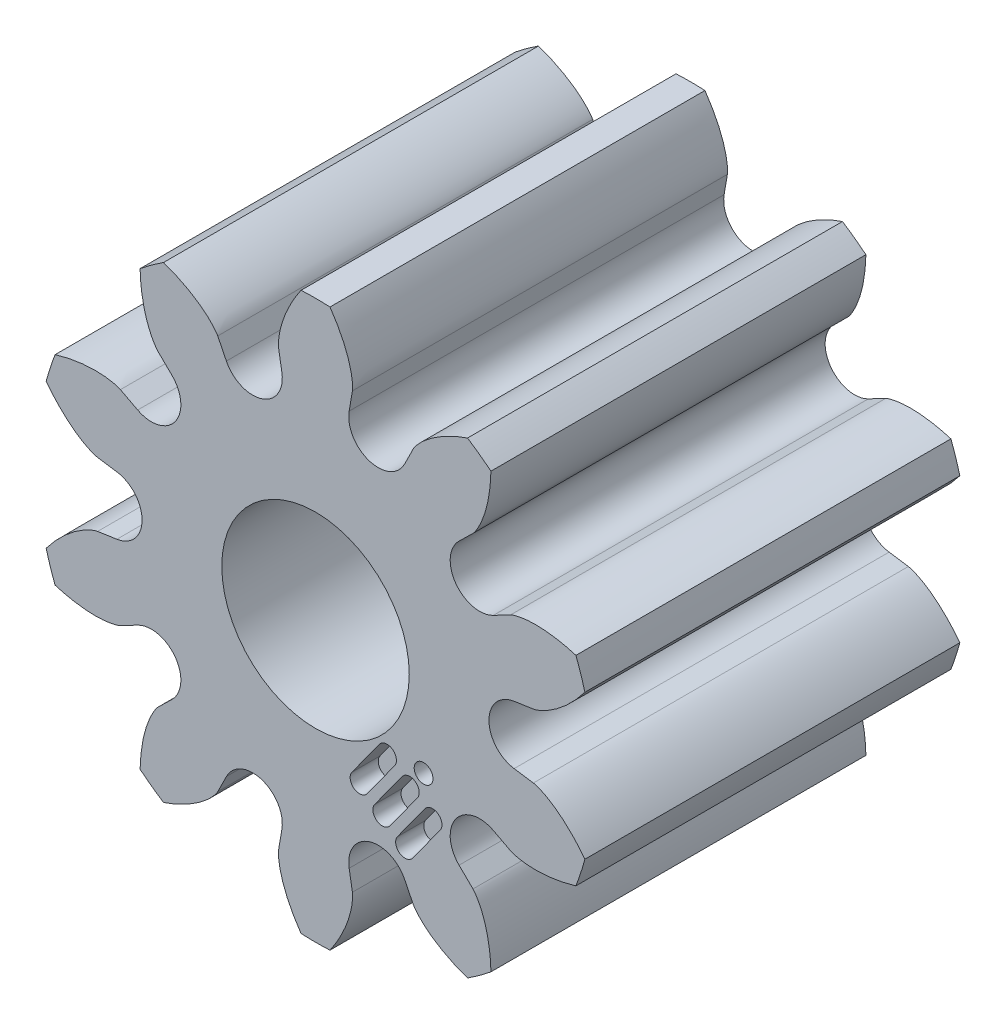
SolidWorks part; units mm, degrees
ref_plane "Front Plane" through (0, 0, 0) normal (0, 0, 1) x (1, 0, 0)
ref_plane "Top Plane" through (0, 0, 0) normal (0, 1, 0) x (1, 0, 0)
ref_plane "Right Plane" through (0, 0, 0) normal (1, 0, 0) x (0, 0, -1)
ref_axis "Axis1" through (0, 0, 4.2) along (0, 0, -1)
sketch "Sketch2" plane through (0, 0, 0) normal (0, 0, 1) x (1, 0, 0)
  circle A0 centre (0, 0) radius 2.975
  dimension "D1" = 5.95
extrude "Boss-Extrude1" add sketch "Sketch2" along normal blind 4
sketch "Sketch1" plane through (0, 0, 0) normal (0, 0, 1) x (1, 0, 0)
  line L1 (2.3243, 0.3413) -> (1.8304, 0.2688) construction
  line L3 (1.8304, -0.2688) -> (2.3243, -0.3413) construction
  line L4 (3.8854, 0) -> (4.3327, 0) construction
  line L6 (2.1188, 0.3112) -> (2.3243, 0.3413)
  line L7 (2.1188, -0.3112) -> (2.3243, -0.3413)
  circle A0 centre (0, 0) radius 1.85 construction
  circle A1 centre (0, 0) radius 2.3492 construction
  circle A6 centre (0, 0) radius 2.975 construction
  arc A7 (2.9584, 0.8934) -> (2.9584, -0.8934) centre (0, 0) cw
  arc A8 (1.8304, 0.2688) -> (1.8304, -0.2688) centre (0, 0) cw construction
  arc A9 (1.85, 0) -> (2.1188, 0.3112) centre (2.1645, 0) cw
  circle A11 centre (0, 0) radius 2.975 construction
  arc A12 (2.3243, 0.3413) -> (2.3243, -0.3413) centre (0, 0) cw construction
  arc A13 (1.85, 0) -> (2.1188, -0.3112) centre (2.1645, 0) ccw
  spline S0 degree 4 poles (2.3243, 0.3413) (2.3278, 0.3419) (2.3344, 0.3434) (2.345, 0.3462) (2.3658, 0.3527) (2.3888, 0.3614) (2.4144, 0.3725) (2.4415, 0.3858) (2.4643, 0.3979) (2.4867, 0.4108) (2.5087, 0.4242) (2.535, 0.4413) (2.5661, 0.4628) (2.6015, 0.4895) (2.6407, 0.5215) (2.6795, 0.5559) (2.7167, 0.5913) (2.7532, 0.6287) (2.7876, 0.666) (2.8221, 0.7064) (2.8532, 0.7446) (2.8867, 0.789) (2.9133, 0.8254) (2.9467, 0.8752) (2.966, 0.9051) (2.988, 0.9407) (2.9974, 0.9568) (3.0033, 0.9667) knots 0 0 0 0 0 0.015084 0.028532 0.04661 0.092111 0.119476 0.146842 0.174209 0.201575 0.228941 0.256307 0.307035 0.361767 0.4165 0.471232 0.525964 0.580697 0.635429 0.690161 0.744894 0.799626 0.854358 0.909091 0.954545 1 1 1 1 1 construction
  spline S1 degree 4 poles (2.3243, 0.3413) (2.3278, 0.3419) (2.3344, 0.3434) (2.345, 0.3462) (2.3658, 0.3527) (2.3888, 0.3614) (2.4144, 0.3725) (2.4415, 0.3858) (2.4643, 0.3979) (2.4867, 0.4108) (2.5087, 0.4242) (2.535, 0.4413) (2.5661, 0.4628) (2.6015, 0.4895) (2.6407, 0.5215) (2.6795, 0.5559) (2.7167, 0.5913) (2.7532, 0.6287) (2.7876, 0.666) (2.8221, 0.7064) (2.8532, 0.7446) (2.8867, 0.789) (2.9133, 0.8254) (2.9395, 0.8644) (2.9521, 0.8835) (2.9584, 0.8934) knots 0 0 0 0 0 0.015084 0.028532 0.04661 0.092111 0.119476 0.146842 0.174209 0.201575 0.228941 0.256307 0.307035 0.361767 0.4165 0.471232 0.525964 0.580697 0.635429 0.690161 0.744894 0.799626 0.854358 0.909091 0.909091 0.909091 0.909091 0.909091
  spline S2 degree 4 poles (2.3243, -0.3413) (2.3278, -0.3419) (2.3344, -0.3434) (2.345, -0.3462) (2.3658, -0.3527) (2.3888, -0.3614) (2.4144, -0.3725) (2.4415, -0.3858) (2.4643, -0.3979) (2.4867, -0.4108) (2.5087, -0.4242) (2.535, -0.4413) (2.5661, -0.4628) (2.6015, -0.4895) (2.6407, -0.5215) (2.6795, -0.5559) (2.7167, -0.5913) (2.7532, -0.6287) (2.7876, -0.666) (2.8221, -0.7064) (2.8532, -0.7446) (2.8867, -0.789) (2.9133, -0.8254) (2.9467, -0.8752) (2.966, -0.9051) (2.988, -0.9407) (2.9974, -0.9568) (3.0033, -0.9667) knots 0 0 0 0 0 0.015084 0.028532 0.04661 0.092111 0.119476 0.146842 0.174209 0.201575 0.228941 0.256307 0.307035 0.361767 0.4165 0.471232 0.525964 0.580697 0.635429 0.690161 0.744894 0.799626 0.854358 0.909091 0.954545 1 1 1 1 1 construction
  spline S3 degree 4 poles (2.3243, -0.3413) (2.3278, -0.3419) (2.3344, -0.3434) (2.345, -0.3462) (2.3658, -0.3527) (2.3888, -0.3614) (2.4144, -0.3725) (2.4415, -0.3858) (2.4643, -0.3979) (2.4867, -0.4108) (2.5087, -0.4242) (2.535, -0.4413) (2.5661, -0.4628) (2.6015, -0.4895) (2.6407, -0.5215) (2.6795, -0.5559) (2.7167, -0.5913) (2.7532, -0.6287) (2.7876, -0.666) (2.8221, -0.7064) (2.8532, -0.7446) (2.8867, -0.789) (2.9133, -0.8254) (2.9395, -0.8644) (2.9521, -0.8835) (2.9584, -0.8934) knots 0 0 0 0 0 0.015084 0.028532 0.04661 0.092111 0.119476 0.146842 0.174209 0.201575 0.228941 0.256307 0.307035 0.361767 0.4165 0.471232 0.525964 0.580697 0.635429 0.690161 0.744894 0.799626 0.854358 0.909091 0.909091 0.909091 0.909091 0.909091
  dimension "D1" = 3.7
  dimension "D2" = 4.6985
  dimension "D3" = 5.95
  dimension "D4" = 5.95
extrude "Cut-Extrude2" cut sketch "Sketch1" along normal through all
pattern_circular "CirPattern1" count 10 over 360 about axis through (0, 0, 4.2) along (0, 0, -1) of "Cut-Extrude2"
sketch "Sketch3" plane through (0, 0, 0) normal (0, 0, 1) x (1, 0, 0)
  circle A0 centre (0, 0) radius 1
  dimension "D1" = 2
extrude "Cut-Extrude3" cut sketch "Sketch3" along normal through all
sketch "Sketch4" [suppressed] plane through (0, 0, 0) normal (0, 0, 1) x (1, 0, 0)
  circle A0 centre (-1.425, 0) radius 0.1
  spline S0 degree 1 poles (0, 0) (-1.425, 0) knots 0 0 1 1 construction
  spline S1 degree 1 poles (0, 0) (-1.425, 0) knots 0 0 1 1 construction
  dimension "D1" = 0.2
extrude "LocationCut" [suppressed] cut sketch "Sketch4" against normal through all both and the other way through all
sketch "Sketch5" [suppressed] plane through (0, 0, 0) normal (0, 0, 1) x (1, 0, 0)
  circle A0 centre (-0.4403, -1.3553) radius 0.1
  spline S0 degree 4 poles (0.0444, 0.1366) (0.0427, 0.1313) (0.0387, 0.1192) (0.0364, 0.112) (0.0216, 0.0664) (0.0029, 0.0091) (-0.0129, -0.0397) (-0.0535, -0.1648) (-0.0781, -0.2403) (-0.1122, -0.3454) (-0.1367, -0.4206) (-0.1626, -0.5004) (-0.1847, -0.5683) (-0.2079, -0.6399) (-0.2298, -0.7074) (-0.2509, -0.7721) (-0.2697, -0.83) (-0.287, -0.8833) (-0.3035, -0.9341) (-0.3206, -0.9868) (-0.3382, -1.0409) (-0.3537, -1.0887) (-0.3703, -1.1398) (-0.3839, -1.1816) (-0.4009, -1.2337) (-0.4134, -1.2722) (-0.4355, -1.3402) (-0.4438, -1.3658) (-0.4625, -1.4234) (-0.4697, -1.4456) (-0.4783, -1.4719) (-0.4812, -1.4811) (-0.4834, -1.4877) (-0.4845, -1.4911) knots 0 0 0 0 0 0.010417 0.020833 0.041667 0.083333 0.145671 0.208009 0.267342 0.324672 0.369982 0.413075 0.452591 0.497901 0.542139 0.581511 0.610383 0.640797 0.673373 0.705996 0.740957 0.77184 0.79428 0.826344 0.853073 0.883495 0.916667 0.947038 0.971084 0.985542 0.992771 1 1 1 1 1 construction
  spline S1 degree 4 poles (0, 0) (-0.0069, -0.0211) (-0.0204, -0.0628) (-0.0535, -0.1648) (-0.0781, -0.2403) (-0.1122, -0.3454) (-0.1367, -0.4206) (-0.1626, -0.5004) (-0.1847, -0.5683) (-0.2079, -0.6399) (-0.2298, -0.7074) (-0.2509, -0.7721) (-0.2697, -0.83) (-0.287, -0.8833) (-0.3035, -0.9341) (-0.3206, -0.9868) (-0.3382, -1.0409) (-0.3537, -1.0887) (-0.3703, -1.1398) (-0.3839, -1.1816) (-0.4009, -1.2337) (-0.4134, -1.2722) (-0.4299, -1.3231) (-0.4367, -1.344) (-0.4403, -1.3553) knots 0.083333 0.083333 0.083333 0.083333 0.083333 0.145671 0.208009 0.267342 0.324672 0.369982 0.413075 0.452591 0.497901 0.542139 0.581511 0.610383 0.640797 0.673373 0.705996 0.740957 0.77184 0.79428 0.826344 0.853073 0.883495 0.916667 0.916667 0.916667 0.916667 0.916667 construction
  dimension "D1" = 0.2
extrude "S2LocationCut" [suppressed] cut sketch "Sketch5" against normal through all both and the other way through all
sketch "Sketch6" plane through (0, 0, 0) normal (0, 0, 1) x (1, 0, 0)
  circle A0 centre (1.1528, -0.8376) radius 0.1
  spline S0 degree 4 poles (-0.1162, 0.0844) (-0.1123, 0.0816) (-0.1001, 0.0727) (-0.0972, 0.0706) (-0.0542, 0.0394) (-0.008, 0.0058) (0.038, -0.0276) (0.1475, -0.1072) (0.2176, -0.1581) (0.3138, -0.228) (0.3884, -0.2822) (0.4647, -0.3376) (0.5272, -0.383) (0.5888, -0.4278) (0.6415, -0.4661) (0.6953, -0.5052) (0.7461, -0.5421) (0.7915, -0.5751) (0.8356, -0.6071) (0.8793, -0.6389) (0.9216, -0.6696) (0.9631, -0.6998) (1.0029, -0.7287) (1.0349, -0.7519) (1.0719, -0.7788) (1.0978, -0.7976) (1.1431, -0.8305) (1.1645, -0.8461) (1.212, -0.8806) (1.229, -0.8929) (1.2544, -0.9114) (1.261, -0.9162) (1.2659, -0.9197) (1.2684, -0.9216) knots 0 0 0 0 0 0.010417 0.020833 0.041667 0.083333 0.14901 0.214686 0.279361 0.34003 0.394259 0.450635 0.487313 0.527902 0.568491 0.605347 0.641512 0.675567 0.699462 0.732706 0.768716 0.796045 0.822421 0.843371 0.867803 0.892235 0.916667 0.941265 0.9749 0.98745 0.993725 1 1 1 1 1 construction
  spline S1 degree 4 poles (0, 0) (0.0189, -0.0138) (0.0572, -0.0415) (0.1475, -0.1072) (0.2176, -0.1581) (0.3138, -0.228) (0.3884, -0.2822) (0.4647, -0.3376) (0.5272, -0.383) (0.5888, -0.4278) (0.6415, -0.4661) (0.6953, -0.5052) (0.7461, -0.5421) (0.7915, -0.5751) (0.8356, -0.6071) (0.8793, -0.6389) (0.9216, -0.6696) (0.9631, -0.6998) (1.0029, -0.7287) (1.0349, -0.7519) (1.0719, -0.7788) (1.0978, -0.7976) (1.1317, -0.8223) (1.1458, -0.8325) (1.1528, -0.8376) knots 0.083333 0.083333 0.083333 0.083333 0.083333 0.14901 0.214686 0.279361 0.34003 0.394259 0.450635 0.487313 0.527902 0.568491 0.605347 0.641512 0.675567 0.699462 0.732706 0.768716 0.796045 0.822421 0.843371 0.867803 0.892235 0.916667 0.916667 0.916667 0.916667 0.916667 construction
  dimension "D1" = 0.2
extrude "S3LocationCut" cut sketch "Sketch6" against normal through all both and the other way through all
sketch "Sketch7" [suppressed] plane through (0, 0, 4) normal (0, 0, 1) x (1, 0, 0)
  line L0 (-1.425, 0.85) -> (-1.425, 0.35) construction
  line L2 (-1.525, 0.85) -> (-1.525, 0.35)
  line L4 (-1.325, 0.85) -> (-1.325, 0.35)
  line L5 (-1.425, 0.6) -> (-2.6866, 0.6) construction
  arc A0 (-1.525, 0.85) -> (-1.325, 0.85) centre (-1.425, 0.85) cw
  arc A1 (-1.525, 0.35) -> (-1.325, 0.35) centre (-1.425, 0.35) ccw
  spline S0 degree 1 poles (0, 0) (-1.425, 0) knots 0 0 1 1 construction
  dimension "D1" = 0.2
  dimension "D2" = 0.5
  dimension "D3" = 0.6
extrude "Cut-Extrude4" [suppressed] cut sketch "Sketch7" against normal blind 0.2 and the other way through all
sketch "Sketch8" [suppressed] plane through (0, 0, 4) normal (0, 0, 1) x (1, 0, 0)
  line L0 (-0.9159, -1.2007) -> (-1.2012, -1.108) construction
  line L2 (-0.885, -1.1056) -> (-1.1703, -1.0129)
  line L4 (-0.9468, -1.2959) -> (-1.2321, -1.2031)
  line L5 (-1.3701, -2.1132) -> (-1.0585, -1.1544) construction
  line L6 (-1.0086, -1.4861) -> (-1.2939, -1.3934)
  line L7 (-1.0704, -1.6763) -> (-1.3557, -1.5836)
  line L8 (-1.0395, -1.5812) -> (-1.3248, -1.4885) construction
  arc A0 (-0.885, -1.1056) -> (-0.9468, -1.2959) centre (-0.9159, -1.2007) cw
  arc A1 (-1.1703, -1.0129) -> (-1.2321, -1.2031) centre (-1.2012, -1.108) ccw
  arc A2 (-1.0086, -1.4861) -> (-1.0704, -1.6763) centre (-1.0395, -1.5812) cw
  arc A3 (-1.2939, -1.3934) -> (-1.3557, -1.5836) centre (-1.3248, -1.4885) ccw
  spline S0 degree 4 poles (0, 0) (-0.0069, -0.0211) (-0.0204, -0.0628) (-0.0535, -0.1648) (-0.0781, -0.2403) (-0.1122, -0.3454) (-0.1367, -0.4206) (-0.1626, -0.5004) (-0.1847, -0.5683) (-0.2079, -0.6399) (-0.2298, -0.7074) (-0.2509, -0.7721) (-0.2697, -0.83) (-0.287, -0.8833) (-0.3035, -0.9341) (-0.3206, -0.9868) (-0.3382, -1.0409) (-0.3537, -1.0887) (-0.3703, -1.1398) (-0.3839, -1.1816) (-0.4009, -1.2337) (-0.4134, -1.2722) (-0.4299, -1.3231) (-0.4367, -1.344) (-0.4403, -1.3553) knots 0.083333 0.083333 0.083333 0.083333 0.083333 0.145671 0.208009 0.267342 0.324672 0.369982 0.413075 0.452591 0.497901 0.542139 0.581511 0.610383 0.640797 0.673373 0.705996 0.740957 0.77184 0.79428 0.826344 0.853073 0.883495 0.916667 0.916667 0.916667 0.916667 0.916667 construction
  dimension "D1" = 0.2
  dimension "D2" = 0.3
  dimension "D4" = 0.5
  dimension "D5" = 0.4
  dimension "D3" = 2
extrude "Cut-Extrude5" [suppressed] cut sketch "Sketch8" against normal blind 0.5
sketch "Sketch9" plane through (0, 0, 4) normal (0, 0, 1) x (1, 0, 0)
  line L0 (0.712, -1.4444) -> (1.0059, -1.0398) construction
  line L1 (0.7929, -1.5031) -> (1.0868, -1.0986)
  line L3 (0.6311, -1.3856) -> (0.925, -0.9811)
  line L4 (0.859, -1.2421) -> (0.7858, -1.189) construction
  line L5 (1.0356, -1.6795) -> (1.3295, -1.275)
  line L6 (0.8738, -1.5619) -> (1.1677, -1.1574)
  line L7 (0.9547, -1.6207) -> (1.2486, -1.2162) construction
  line L8 (0.5502, -1.3268) -> (0.8441, -0.9223)
  line L9 (0.3884, -1.2092) -> (0.6823, -0.8047)
  line L10 (0.4693, -1.268) -> (0.7632, -0.8635) construction
  line L11 (0.9547, -1.6207) -> (1.0356, -1.6795) construction
  line L12 (0.712, -1.4444) -> (0.7929, -1.5031) construction
  line L13 (0.4693, -1.268) -> (0.5502, -1.3268) construction
  line L14 (0.4693, -1.268) -> (0.712, -1.4444) construction
  line L15 (0.712, -1.4444) -> (0.9547, -1.6207) construction
  arc A0 (0.6311, -1.3856) -> (0.7929, -1.5031) centre (0.712, -1.4444) ccw
  arc A1 (0.925, -0.9811) -> (1.0868, -1.0986) centre (1.0059, -1.0398) cw
  arc A2 (0.8738, -1.5619) -> (1.0356, -1.6795) centre (0.9547, -1.6207) ccw
  arc A3 (1.1677, -1.1574) -> (1.3295, -1.275) centre (1.2486, -1.2162) cw
  arc A4 (0.3884, -1.2092) -> (0.5502, -1.3268) centre (0.4693, -1.268) ccw
  arc A5 (0.6823, -0.8047) -> (0.8441, -0.9223) centre (0.7632, -0.8635) cw
  spline S0 degree 4 poles (0, 0) (0.0189, -0.0138) (0.0572, -0.0415) (0.1475, -0.1072) (0.2176, -0.1581) (0.3138, -0.228) (0.3884, -0.2822) (0.4647, -0.3376) (0.5272, -0.383) (0.5888, -0.4278) (0.6415, -0.4661) (0.6953, -0.5052) (0.7461, -0.5421) (0.7915, -0.5751) (0.8356, -0.6071) (0.8793, -0.6389) (0.9216, -0.6696) (0.9631, -0.6998) (1.0029, -0.7287) (1.0349, -0.7519) (1.0719, -0.7788) (1.0978, -0.7976) (1.1317, -0.8223) (1.1458, -0.8325) (1.1528, -0.8376) knots 0.083333 0.083333 0.083333 0.083333 0.083333 0.14901 0.214686 0.279361 0.34003 0.394259 0.450635 0.487313 0.527902 0.568491 0.605347 0.641512 0.675567 0.699462 0.732706 0.768716 0.796045 0.822421 0.843371 0.867803 0.892235 0.916667 0.916667 0.916667 0.916667 0.916667 construction
  dimension "D1" = 0.3
  dimension "D2" = 0.2
  dimension "D5" = 0.5
  dimension "D3" = 0.5
extrude "Cut-Extrude6" cut sketch "Sketch9" against normal blind 0.3
equation "\"R1_NumTeeth\"= 52"
equation "\"R2_teeth\"= 51"
equation "\"P1_teeth\"= 10"
equation "\"sun_teeth\"= \"R1_NumTeeth\" - 2 * \"P1_teeth\""
equation "\"P2_teeth\" = 10"
equation "\"Nteeth\"= \"P2_teeth\""
equation "\"S1_Module\"= 0.5\t\t'tooth per mm"
equation "\"module\"= \"S1_Module\""
equation "\"S1_PressureAngle\"= 20'deg. leave unitless"
equation "\"pressure_angle\"= \"S1_PressureAngle\" * pi / 180"
equation "\"Planet_profile_shift\" = -0.05"
equation "\"x_shift\"= \"Planet_profile_shift\""
equation "\"r_p\"= \"module\" * \"Nteeth\" / 2'pitch circle radius"
equation "\"r_b\"= \"r_p\" * cos ( \"pressure_angle\" )'base circle radius"
equation "\"r_a\"= \"r_p\" + \"module\" * ( 1 + \"x_shift\" )'addendum"
equation "\"r_f\"= \"r_p\" - \"module\" * ( 1.25 - \"x_shift\" )'dedendum"
equation "\"tmax\"= sqr ( ( \"r_a\" / \"r_b\" ) * ( \"r_a\" / \"r_b\" ) - 1 ) * 1.1"
equation "\"t_p\"= sqr ( ( \"r_p\" / \"r_b\" ) ^ 2 - 1 )'t at pitch circle"
equation "\"x_p\"= \"r_b\" * ( cos ( \"t_p\" ) + \"t_p\" * sin ( \"t_p\" ) )"
equation "\"y_p\"= \"r_b\" * ( sin ( \"t_p\" ) - \"t_p\" * cos ( \"t_p\" ) )"
equation "\"theta_p\"= atn ( \"y_p\" / \"x_p\" )"
equation "\"des_ang\"= ( pi / 2 - 2 * \"x_shift\" * tan ( \"pressure_angle\" ) ) / \"Nteeth\""
equation "\"delta\"= \"des_ang\" - \"theta_p\""
equation "\"delta2\"= \"delta\" + 2 * pi * ( \"Nteeth\" - 1 ) / \"Nteeth\""
equation "\"height\"=4"
equation "\"Planet_broachcutter_offset\" = -0.0"
equation "\"fillet\"= 0.1 'radius of the fillet at the base of the tooth near the dedendum"
equation "\"halftooth\"= pi / \"Nteeth\""
equation "\"S1_carrier_radius\"= \"P1_teeth\" * \"S1_Module\" / 2  + \"sun_teeth\" * \"S1_Module\" / 2"
equation "\"S2_Module\"= 0.5121951219512195\t\t\t'stage two gear modules CAN be different from stage 1; this makes things a lot more complicated though so try and avoid it if you can"
equation "\"S2_PressureAngle\"= \"S1_PressureAngle\"'stage two pressure angle can be different, but for simplicity keep it the same"
equation "\"Ring_profile_shift\" = 0.05"
equation "\"Ring_broachcutter_offset\" = 0.0"
equation "\"Nteeth_bcg\"= \"P2_teeth\""
equation "\"r_p_bcg\"= \"module\" * \"Nteeth_bcg\" / 2"
equation "\"r_a_bcg\"= \"r_p_bcg\" + \"module\" * ( 1 + \"x_shift\" )"
equation "\"r_f_bcg\"= \"r_p_bcg\" - \"module\" * ( 1.25 - \"x_shift\" )"
equation "\"involute_offset\"= - \"r_a\" + \"r_a_bcg\" + \"Planet_broachcutter_offset\""
equation "\"D1@Sketch2\"=(\"r_a\"+\"involute_offset\")*2"
equation "\"D2@Sketch1\"=(\"r_b\"+\"involute_offset\")*2"
equation "\"D4@Sketch1\"=(\"r_a\"+\"involute_offset\")*2"
equation "\"D1@Sketch1\"=(\"r_f\"+\"involute_offset\")*2"
equation "\"Bore\"= 2'center bore diameter"
equation "\"D1@Sketch3\"=\"Bore\""
equation "\"D1@CirPattern1\"=\"Nteeth_bcg\""
equation "\"D1@Boss-Extrude1\"=\"height\""
equation "\"D3@Sketch1\"=\"r_a\"*2"
